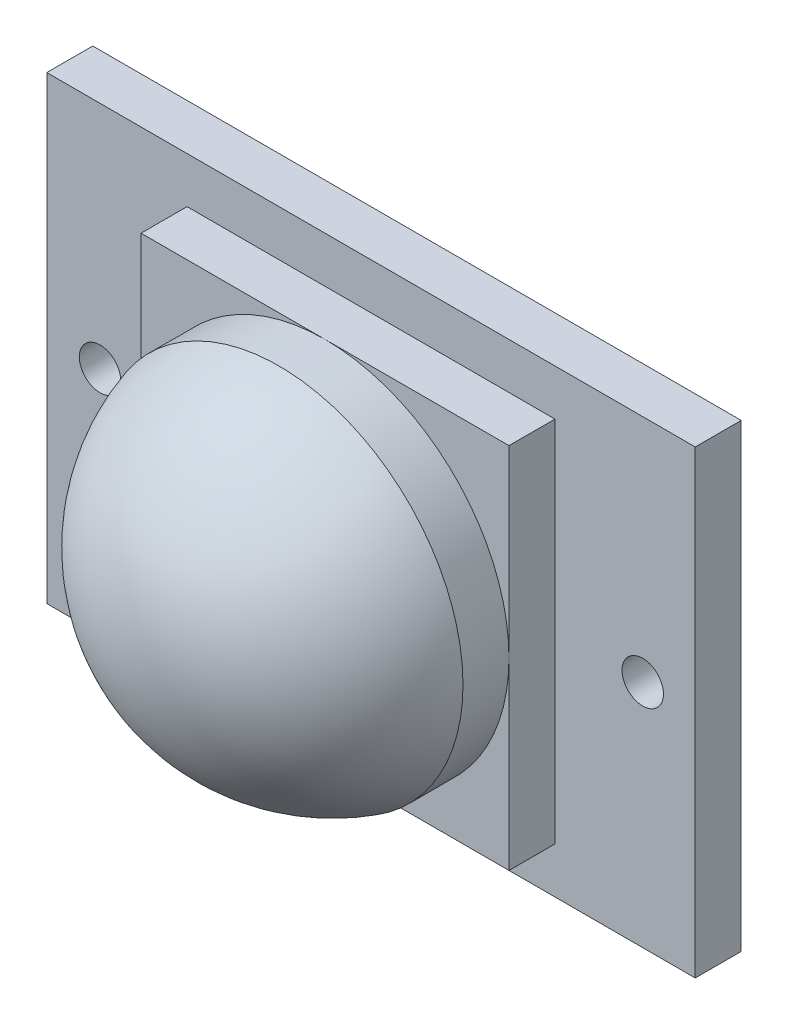
SolidWorks part; units mm, degrees
ref_plane "Front Plane" through (0, 0, 0) normal (0, 0, 1) x (1, 0, 0)
ref_plane "Top Plane" through (0, 0, 0) normal (0, 1, 0) x (1, 0, 0)
ref_plane "Right Plane" through (0, 0, 0) normal (1, 0, 0) x (0, 0, -1)
sketch "Sketch1" plane through (0, 0, 0) normal (0, 0, 1) x (1, 0, 0)
  line L1 (0, 0) -> (35.814, 0)
  line L2 (0, 0) -> (0, 25.4)
  line L3 (0, 25.4) -> (35.814, 25.4)
  line L4 (35.814, 0) -> (35.814, 25.4)
  dimension "D1" = 35.814
  dimension "D2" = 25.4
extrude "Boss-Extrude1" add sketch "Sketch1" along normal blind 2.54
sketch "Sketch2" plane through (0, 0, 2.54) normal (0, 0, 1) x (1, 0, 0)
  line L1 (0, 0) -> (35.814, 0) construction
  line L2 (35.814, 25.4) -> (0, 25.4) construction
  line L3 (35.814, 0) -> (35.814, 25.4) construction
  circle A0 centre (2.942, 12.7) radius 1.143
  circle A1 centre (32.914, 12.7) radius 1.143
  dimension "D1" = 2.286
  dimension "D2" = 2.286
  dimension "D3" = 29.972
  dimension "D4" = 12.7
  dimension "D5" = 12.7
  dimension "D6" = 2.9
extrude "Cut-Extrude1" cut sketch "Sketch2" against normal blind 2.54
sketch "Sketch3" plane through (0, 0, 2.54) normal (0, 0, 1) x (1, 0, 0)
  line L0 (35.814, 25.4) -> (0, 25.4) construction
  line L1 (7.747, 22.86) -> (28.067, 22.86)
  line L2 (7.747, 22.86) -> (7.747, 2.54)
  line L3 (7.747, 2.54) -> (28.067, 2.54)
  line L4 (28.067, 22.86) -> (28.067, 2.54)
  line L5 (35.814, 0) -> (35.814, 25.4) construction
  point P4 (17.907, 22.86)
  point P7 (17.907, 25.4)
  point P8 (28.067, 12.7)
  point P11 (35.814, 12.7)
  dimension "D1" = 20.32
  dimension "D2" = 20.32
  dimension "D3" = 0
  dimension "D4" = 0
extrude "Boss-Extrude3" add sketch "Sketch3" along normal blind 2.54
sketch "Sketch4" plane through (0, 0, 5.08) normal (0, 0, 1) x (1, 0, 0)
  line L0 (35.814, 25.4) -> (0, 25.4) construction
  line L1 (0, 25.4) -> (0, 0) construction
  circle A0 centre (17.907, 12.7) radius 10.16
  dimension "D1" = 20.32
  dimension "D2" = 12.7
  dimension "D3" = 17.907
extrude "Boss-Extrude4" add sketch "Sketch4" along normal blind 2.54
dome "Dome3" faces to dome 1 distance 7.62 reverse direction no elliptical dome no face at (28.067, 12.7, 7.62) parameters "D1"=7.62
